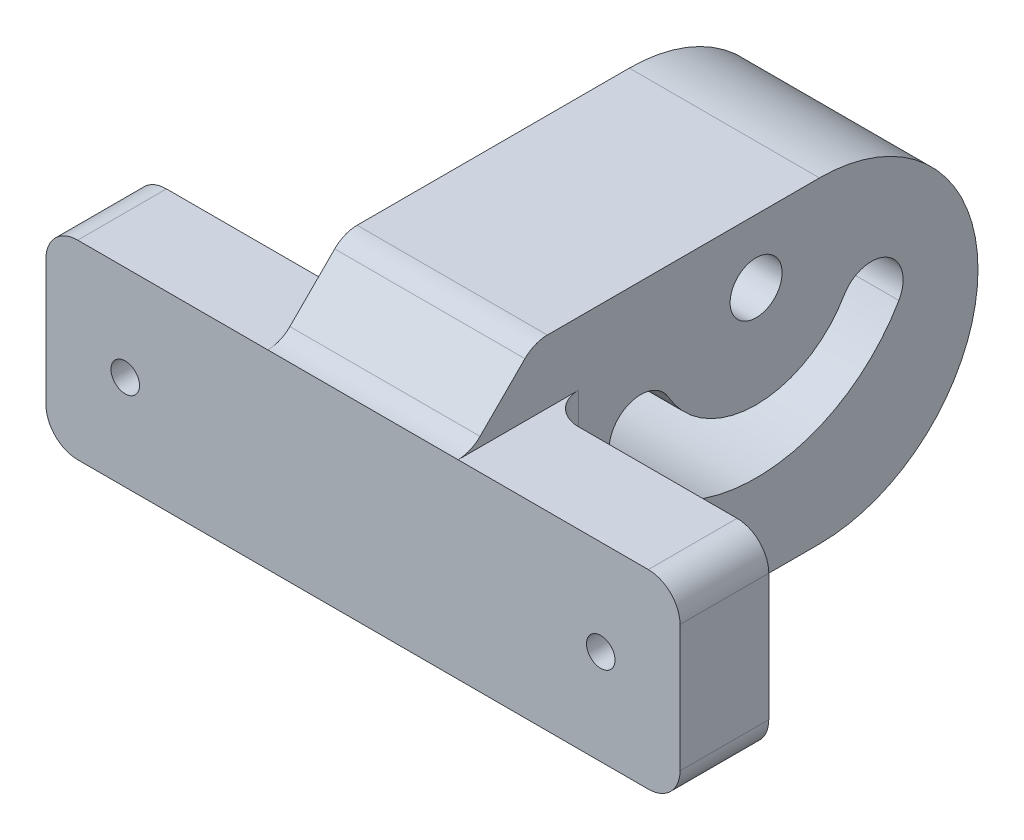
SolidWorks part; units mm, degrees
ref_plane "Front Plane" through (0, 0, 0) normal (0, 0, 1) x (1, 0, 0)
ref_plane "Top Plane" through (0, 0, 0) normal (0, 1, 0) x (1, 0, 0)
ref_plane "Right Plane" through (0, 0, 0) normal (1, 0, 0) x (0, 0, -1)
sketch "Sketch1" plane through (0, 0, -7) normal (0, 0, -1) x (-1, 0, 0)
  line L0 (0, 0) -> (0, -44) construction
  line L1 (-50, -14) -> (50, -14)
  line L2 (-50, -14) -> (-50, -44)
  line L3 (-50, -44) -> (50, -44)
  line L4 (50, -14) -> (50, -44)
  line L5 (-37.5, -29) -> (37.5, -29) construction
  dimension "D1" = 100
  dimension "D2" = 30
extrude "Boss-Extrude1" add sketch "Sketch1" along normal blind 14
sketch "Sketch2" plane through (0, 0, -21) normal (0, 0, -1) x (-1, 0, 0)
  line L0 (0, 0) -> (0, -44) construction
  line L1 (-50, -44) -> (50, -44) construction
  line L2 (-50, -29) -> (50, -29) construction
  line L3 (-50, -14) -> (-50, -44) construction
  line L4 (50, -44) -> (50, -14) construction
  circle A0 centre (-37.5, -29) radius 2.25
  circle A1 centre (37.5, -29) radius 2.25
  dimension "D2" = 4.5
  dimension "D1" = 75
extrude "Cut-Extrude1" cut sketch "Sketch2" against normal up to surface (14 mm away) up to face at (0, -29, -7)
sketch "Sketch3" plane through (0, 0, -21) normal (0, 0, -1) x (-1, 0, 0)
  circle A0 centre (-37.5, -29) radius 4.5
  circle A1 centre (37.5, -29) radius 4.5
  dimension "D1" = 9
extrude "Cut-Extrude2" cut sketch "Sketch3" against normal blind 4.4
sketch "Sketch5" plane through (0, 0, 0) normal (1, 0, 0) x (0, 0, -1)
  line L0 (9, -14) -> (19, -4)
  line L1 (21, -14) -> (7, -14) construction
  line L4 (19, -4) -> (89, -4)
  line L5 (89, -4) -> (89, -54)
  line L6 (21, -29) -> (105.9177, -29) construction
  line L7 (21, -14) -> (21, -44) construction
  line L8 (7, -105) -> (7, -13) construction
  line L9 (9, -14) -> (9, -44)
  line L10 (9, -44) -> (19, -54)
  line L11 (19, -54) -> (89, -54)
  point P18 (9, -29)
  point P19 (89, -29)
  dimension "D1" = 70
  dimension "D2" = 2
  dimension "D3" = 45
  dimension "D4" = 25
extrude "Boss-Extrude2" add sketch "Sketch5" along normal mid plane 30
sketch "Sketch6" plane through (0, 0, 0) normal (1, 0, 0) x (0, 0, -1)
  line L0 (89, -4) -> (19, -4) construction
  line L1 (89, -54) -> (89, -4) construction
  circle A0 centre (54, -14) radius 4.1
  dimension "D1" = 10
  dimension "D2" = 35
  dimension "D3" = 8.2
extrude "Cut-Extrude3" cut sketch "Sketch6" against normal through all both and the other way through all
fillet "Fillet1" radius 25 2 edges at (0, -4, -89) (0, -54, -89)
sketch "Sketch7" plane through (0, 0, 0) normal (1, 0, 0) x (0, 0, -1)
  line L0 (35.8135, -24.5) -> (54, -14) construction
  line L1 (54, -14) -> (54, -35) construction
  line L2 (54, -14) -> (72.1865, -24.5) construction
  circle A0 centre (54, -14) radius 21 construction
  arc A2 (35.8135, -24.5) -> (72.1865, -24.5) centre (54, -14) ccw construction
  arc A3 (31.4833, -27) -> (76.5167, -27) centre (54, -14) ccw
  arc A4 (40.1436, -22) -> (67.8564, -22) centre (54, -14) ccw
  arc A5 (40.1436, -22) -> (31.4833, -27) centre (35.8135, -24.5) ccw
  arc A6 (76.5167, -27) -> (67.8564, -22) centre (72.1865, -24.5) ccw
  point P5 (54, -35)
  dimension "D1" = 42
  dimension "D2" = 60
  dimension "D3" = 60
  dimension "D4" = 10
extrude "Cut-Extrude5" cut sketch "Sketch7" against normal through all both and the other way through all
fillet "Fillet2" radius 5 10 edges at (15, -29, -21) (0, -14, -9) (0, -44, -9) (-15, -29, -21) (50, -14, -14) (50, -44, -14) (-50, -44, -14) (-50, -14, -14) (0, -54, -19) (0, -4, -19)
